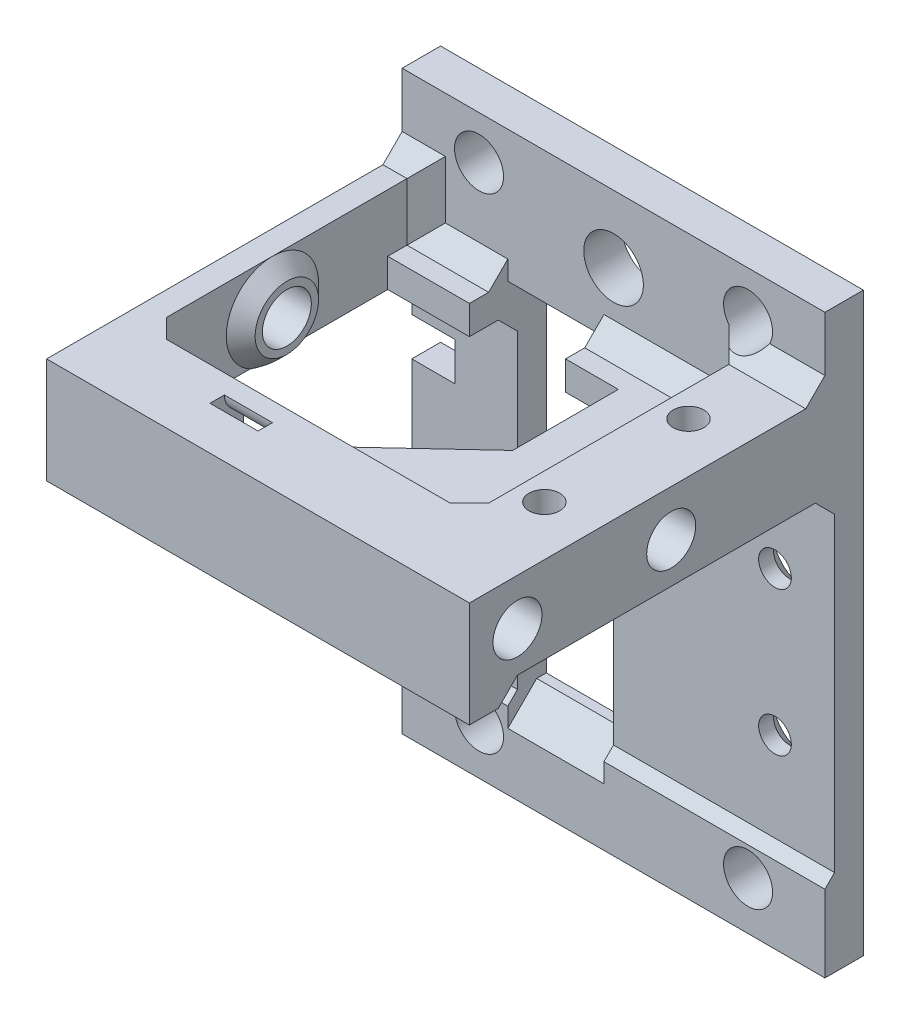
SolidWorks part; units mm, degrees
ref_plane "Front Plane" through (0, 0, 0) normal (0, 0, 1) x (1, 0, 0)
ref_plane "Top Plane" through (0, 0, 0) normal (0, 1, 0) x (1, 0, 0)
ref_plane "Right Plane" through (0, 0, 0) normal (1, 0, 0) x (0, 0, -1)
sketch "Sketch1" plane through (0, 0, 0) normal (0, 1, 0) x (1, 0, 0)
  line L0 (-19.5, 12.5) -> (-19.5, -12.5)
  line L1 (-22, -20.5) -> (22, -20.5)
  line L2 (-22, -20.5) -> (-22, 20.5)
  line L3 (-22, 20.5) -> (22, 20.5)
  line L4 (22, -20.5) -> (22, 20.5)
  line L5 (-22, -20.5) -> (22, 20.5) construction
  line L6 (-22, 20.5) -> (22, -20.5) construction
  line L7 (-19.5, 12.5) -> (4.5, 12.5)
  line L8 (4.5, 12.5) -> (4.5, 1.5)
  line L9 (-19.5, -12.5) -> (-10.5244, -12.5)
  line L10 (-10.5244, -12.5) -> (4.5, 1.5)
  circle A0 centre (16.8, -7.5) radius 1.6
  circle A1 centre (16.8, 7.5) radius 1.6
  point P0 (0, 0)
  dimension "D9" = 3.2
  dimension "D12" = 3.2
  dimension "D1" = 44
  dimension "D2" = 41
  dimension "D3" = 2.5
  dimension "D4" = 25
  dimension "D5" = 8
  dimension "D6" = 24
  dimension "D7" = 11
  dimension "D8" = 5.2
  dimension "D10" = 13
  dimension "D11" = 15
extrude "Boss-Extrude1" add sketch "Sketch1" along normal blind 3
sketch "Sketch2" plane through (0, 3, 0) normal (0, 1, 0) x (1, 0, 0)
  line L0 (-22, 20.5) -> (-22, -20.5) construction
  line L1 (22, 20.5) -> (-22, 20.5)
  line L2 (22, 20.5) -> (22, 16.5)
  line L3 (22, 16.5) -> (-22, 16.5)
  line L4 (-22, 20.5) -> (-22, 16.5)
  dimension "D1" = 4
extrude "Boss-Extrude2" add sketch "Sketch2" along normal blind 13.7
sketch "Sketch3" plane through (0, 0, 0) normal (0, -1, 0) x (1, 0, 0)
  line L0 (22, 20.5) -> (22, -20.5) construction
  line L1 (-22, -20.5) -> (22, -20.5)
  line L2 (-22, -20.5) -> (-22, -17.5)
  line L3 (-22, -17.5) -> (22, -17.5)
  line L4 (22, -20.5) -> (22, -17.5)
  dimension "D1" = 3
extrude "Boss-Extrude3" add sketch "Sketch3" along normal blind 41.3
sketch "Sketch4" plane through (0, 0, 0) normal (0, -1, 0) x (1, 0, 0)
  line L0 (-22, -17.5) -> (-22, 20.5) construction
  line L1 (22, 20.5) -> (-22, 20.5)
  line L2 (22, 20.5) -> (22, 17.5)
  line L3 (22, 17.5) -> (-22, 17.5)
  line L4 (-22, 20.5) -> (-22, 17.5)
  dimension "D1" = 3
extrude "Boss-Extrude4" add sketch "Sketch4" along normal blind 32.5
sketch "Sketch8" plane through (-22, 0, 0) normal (-1, 0, 0) x (0, 0, 1)
  line L0 (-16.5, -35.3) -> (-17.5, -34.3)
  line L1 (-17.5, -41.3) -> (-16.5, -41.3)
  line L2 (-17.5, -41.3) -> (-17.5, -35.3)
  line L3 (-17.5, -35.3) -> (-16.5, -35.3)
  line L4 (-16.5, -41.3) -> (-16.5, -35.3)
  line L5 (-17.5, -41.3) -> (-17.5, 0) construction
  line L6 (-17.5, -34.3) -> (-17.5, -35.3)
  line M5 (-17.5, -41.3) -> (-17.5, 0)
  dimension "D1" = 1
  dimension "D2" = 6
extrude "Boss-Extrude6" add sketch "Sketch8" against normal up to surface (44 mm away) contours L1 L4 L3 M5 | L3 L0 M5 region at (-22, -34.9667, -17.1667) region at (-22, -38.3, -17) up to face at (22, -10.82, -3.3)
sketch "Sketch9" plane through (0, 0, 20.5) normal (0, 0, 1) x (1, 0, 0)
  line L0 (-22, 3) -> (-22, -32.5) construction
  line L1 (3, -26) -> (10, -26)
  line L2 (3, -26) -> (3, -5)
  line L3 (3, -5) -> (10, -5)
  line L4 (10, -26) -> (10, -5)
  line L5 (22, -32.5) -> (-22, -32.5) construction
  line L6 (22, 3) -> (22, -32.5) construction
  circle A0 centre (15.8, -10) radius 1.6
  circle A1 centre (15.8, -25) radius 1.6
  dimension "D5" = 3.2
  dimension "D6" = 3.2
  dimension "D1" = 25
  dimension "D2" = 7
  dimension "D3" = 21
  dimension "D4" = 6.5
  dimension "D7" = 6.2
  dimension "D8" = 6.2
  dimension "D9" = 15
  dimension "D10" = 7.5
extrude "Cut-Extrude2" cut sketch "Sketch9" against normal up to next
sketch "Sketch12" plane through (0, 3, 0) normal (0, 1, 0) x (1, 0, 0)
  line L0 (-22, 16.5) -> (-22, -20.5) construction
  line L1 (22, -20.5) -> (-22, -20.5)
  line L2 (22, -20.5) -> (22, -12.5)
  line L3 (22, -12.5) -> (-22, -12.5)
  line L4 (-22, -20.5) -> (-22, -12.5)
  line L5 (-19.5, -12.5) -> (-10.5244, -12.5) construction
  line L6 (-19.5, 12.5) -> (-19.5, -12.5) construction
  line L7 (-22, 16.5) -> (-19.5, 16.5)
  line L8 (-22, 16.5) -> (-22, -12.5)
  line L9 (-22, -12.5) -> (-19.5, -12.5)
  line L10 (-19.5, 16.5) -> (-19.5, -12.5)
  line L11 (-22, 16.5) -> (22, 16.5) construction
  line L12 (22, -12.5) -> (14, -12.5)
  line L13 (22, -12.5) -> (22, 16.5)
  line L14 (22, 16.5) -> (14, 16.5)
  line L15 (14, -12.5) -> (14, 16.5)
  circle M6 centre (16.8, 7.5) radius 1.6
  circle M7 centre (16.8, -7.5) radius 1.6
  line M11 (-10.5244, -12.5) -> (-19.5, -12.5)
  line M12 (-19.5, -12.5) -> (-19.5, 12.5)
  line M13 (22, 16.5) -> (-22, 16.5)
  line M14 (-22, 16.5) -> (-22, -20.5)
  line M15 (-22, -20.5) -> (22, -20.5)
  line M16 (22, -20.5) -> (22, 16.5)
  dimension "D1" = 8
extrude "Boss-Extrude7" add sketch "Sketch12" along normal blind 6 contours L15 L3 M16 M13 M7 M6 | L3 M16 M11 M14 M15 | L10 L3 M13 M14 M12 region at (0, 3, 16.5) region at (18.0894, 3, -2.149) region at (-20.75, 3, -2)
sketch "Sketch13" plane through (-22, 0, 0) normal (-1, 0, 0) x (0, 0, 1)
  line L0 (20.5, 9) -> (20.5, -32.5) construction
  line L1 (-17.5, 0) -> (17.5, 0) construction
  line L2 (-17.5, -34.3) -> (-17.5, 0) construction
  circle A0 centre (15.5, 4.2) radius 2.55
  circle A1 centre (-0.5, 4.2) radius 2.55
  dimension "D3" = 5.1
  dimension "D5" = 5.1
  dimension "D1" = 5
  dimension "D2" = 4.2
  dimension "D4" = 17
extrude "Cut-Extrude3" cut sketch "Sketch13" against normal blind 6
sketch "Sketch14" plane through (-19.5, 0, 0) normal (1, 0, 0) x (0, 0, -1)
  circle A0 centre (0.5, 4.2) radius 3.3
  circle A1 centre (0.5, 4.2) radius 2.55
  dimension "D1" = 6.6
extrude "Boss-Extrude9" add sketch "Sketch14" along normal blind 1.5
mirror "Mirror1" about plane through (0, 0, 0) normal (1, 0, 0) of "Cut-Extrude3"
sketch "Sketch15" plane through (0, 0, 20.5) normal (0, 0, 1) x (1, 0, 0)
  point P0 (15.8, -10)
  point P1 (15.8, -25)
hole_wizard "CSK for M3 Flat Head Machine Screw1" positions "Sketch18" profile "Sketch19" countersink size "M3" standard "ANSI Metric" end condition through all
sketch "Sketch18" plane through (0, 0, 20.5) normal (0, 0, 1) x (1, 0, 0)
  point P0 (15.8, -10)
  point P3 (15.8, -25)
sketch "Sketch19" plane through (15.8, -10, 20.5) normal (1, 0, 0) x (0, -1, 0)
  line L0 (0, 0) -> (0, 41)
  line L1 (0, 41) -> (1.7, 41)
  line L2 (1.7, 41) -> (1.7, 1.45)
  line L3 (1.7, 1.45) -> (3.15, 0)
  line L5 (3.15, 0) -> (0, 0)
  line L6 (-1.7, 1.45) -> (-3.15, 0) construction
  line L11 (0, -6.35) -> (0, 107.95) construction
  dimension "Thru Hole Dia." = 3.4
  dimension "Thru Hole Depth" = 41
  dimension "Near C'Sink Dia." = 6.3
  dimension "Near C'Sink Angle" = 90
sketch "Sketch20" plane through (0, 0, -20.5) normal (0, 0, -1) x (-1, 0, 0)
  point P0 (-15.8, -10)
  point P1 (-15.8, -25)
hole_wizard "CSK for M3 Flat Head Machine Screw2" positions "Sketch21" profile "Sketch22" countersink size "M3" standard "ANSI Metric" end condition through all
sketch "Sketch21" plane through (0, 0, -20.5) normal (0, 0, -1) x (-1, 0, 0)
  point P0 (-15.8, -10)
  point P3 (-15.8, -25)
sketch "Sketch22" plane through (15.8, -10, -20.5) normal (1, 0, 0) x (0, 1, 0)
  line L0 (0, 0) -> (0, 41)
  line L1 (0, 41) -> (1.7, 41)
  line L2 (1.7, 41) -> (1.7, 1.45)
  line L3 (1.7, 1.45) -> (3.15, 0)
  line L5 (3.15, 0) -> (0, 0)
  line L6 (-1.7, 1.45) -> (-3.15, 0) construction
  line L11 (0, -6.35) -> (0, 107.95) construction
  dimension "Thru Hole Dia." = 3.4
  dimension "Thru Hole Depth" = 41
  dimension "Near C'Sink Dia." = 6.3
  dimension "Near C'Sink Angle" = 90
sketch "Sketch23" plane through (0, 0, -17.5) normal (0, 0, 1) x (1, 0, 0)
  line L0 (22, -34.3) -> (-22, -34.3) construction
  line L1 (-1, 3) -> (-11, 3)
  line L2 (-1, 3) -> (-1, -34.3)
  line L3 (-1, -34.3) -> (-11, -34.3)
  line L4 (-11, 3) -> (-11, -34.3)
  line L5 (-1, 3) -> (-11, -34.3) construction
  line L6 (-1, -34.3) -> (-11, 3) construction
  line L9 (-22, -34.3) -> (-22, 0) construction
  line L11 (14, 3) -> (-10.5244, 3) construction
  point P0 (-6, -15.65)
  dimension "D1" = 10
  dimension "D2" = 16
extrude "Cut-Extrude4" cut sketch "Sketch23" against normal up to next and the other way up to next
chamfer "Chamfer2" distance 1.5 1 edges at (-19.5, 4.2, -3.8)
chamfer "Chamfer3" distance 2 11 edges at (-15.25, 3, -16.5) (6.5, 3, -16.5) (10.5, 0, -17.5) (-16.5, 0, -17.5) (0, 0, 17.5) (18, 9, -16.5) (-20.75, 9, -16.5) (-19.5, 4.5, 12.5) (14, 6, 12.5) (14, 6, -16.5) (-19.5, 6, -16.5)
sketch "Sketch5" plane through (0, 0, -20.5) normal (0, 0, -1) x (-1, 0, 0)
  line L0 (0, -41.3) -> (0, 16.7) construction
  line L1 (22, -41.3) -> (-22, -41.3) construction
  line L2 (-22, 16.7) -> (22, 16.7) construction
  circle A0 centre (-14, -38.3) radius 2.55
  circle A1 centre (14, -38.3) radius 2.55
  circle A2 centre (-14, 12.2) radius 2.55
  circle A3 centre (14, 12.2) radius 2.55
  circle A4 centre (0, 9.7) radius 3.1
  dimension "D1" = 5.1
  dimension "D4" = 5.1
  dimension "D7" = 6.2
  dimension "D2" = 3
  dimension "D3" = 14
  dimension "D5" = 50.5
  dimension "D6" = 7
extrude "Cut-Extrude1" cut sketch "Sketch5" against normal up to next
sketch "Sketch24" plane through (-1, 0, 0) normal (-1, 0, 0) x (0, 0, 1)
  line L3 (-17.5, -34.3) -> (-19.5, -34.3)
  line L5 (-16.5, -40.85) -> (-16.5, -35.75) construction
  line L6 (-16.5, -37.3) -> (-16.5, -35.3)
  line L7 (-16.5, -41.3) -> (-16.5, -35.3) construction
  line L8 (-19.5, -34.3) -> (-16.5, -37.3)
  line L9 (-16.5, -35.3) -> (-17.5, -34.3)
extrude "Cut-Extrude9" cut sketch "Sketch24" along normal up to surface (10 mm away) up to face at (-11, -5.36, -16.4)
sketch "Sketch25" plane through (0, 0, 12.5) normal (0, 0, -1) x (-1, 0, 0)
  line L0 (22, 16.7) -> (22, -41.3) construction
  line L1 (9.5, 7) -> (4.5, 7)
  line L2 (9.5, 7) -> (9.5, 5.5)
  line L3 (9.5, 5.5) -> (4.5, 5.5)
  line L4 (4.5, 7) -> (4.5, 5.5)
  line L5 (9.5, 7) -> (4.5, 5.5) construction
  line L6 (9.5, 5.5) -> (4.5, 7) construction
  line L7 (-12, 9) -> (17.5, 9) construction
  point P0 (7, 6.25)
  dimension "D1" = 15
  dimension "D2" = 5
  dimension "D3" = 1.5
  dimension "D4" = 2
sketch "Sketch26" plane through (0, 0, -20.5) normal (0, 0, -1) x (-1, 0, 0)
  line L0 (22, 16.7) -> (22, -41.3) construction
  line L1 (22, -6) -> (17.5, -6)
  line L2 (22, -6) -> (22, -10)
  line L3 (22, -10) -> (17.5, -10)
  line L4 (17.5, -6) -> (17.5, -10)
  line L6 (22.55, 0) -> (-22.55, 0) construction
  dimension "D1" = 6
  dimension "D2" = 4
  dimension "D3" = 4.5
extrude "Cut-Extrude11" cut sketch "Sketch26" against normal up to next
revolve "Cut-Revolve1" cut sketch "Sketch25" angle 90 about axis through (0, 9, 12.5) along (-1, 0, 0)
sketch "Sketch27" plane through (0, -41.3, 0) normal (0, -1, 0) x (1, 0, 0)
  line L1 (-22, -20.5) -> (22, -20.5)
  line L2 (-22, -20.5) -> (-22, -16.5)
  line L3 (-22, -16.5) -> (22, -16.5)
  line L4 (22, -20.5) -> (22, -16.5)
extrude "Boss-Extrude10" add sketch "Sketch27" along normal blind 2
sketch "Sketch28" plane through (0, -32.5, 0) normal (0, -1, 0) x (1, 0, 0)
  line L1 (-22, 17.5) -> (22, 17.5)
  line L2 (-22, 17.5) -> (-22, 20.5)
  line L3 (-22, 20.5) -> (22, 20.5)
  line L4 (22, 17.5) -> (22, 20.5)
extrude "Cut-Extrude13" cut sketch "Sketch28" against normal blind 30.5
